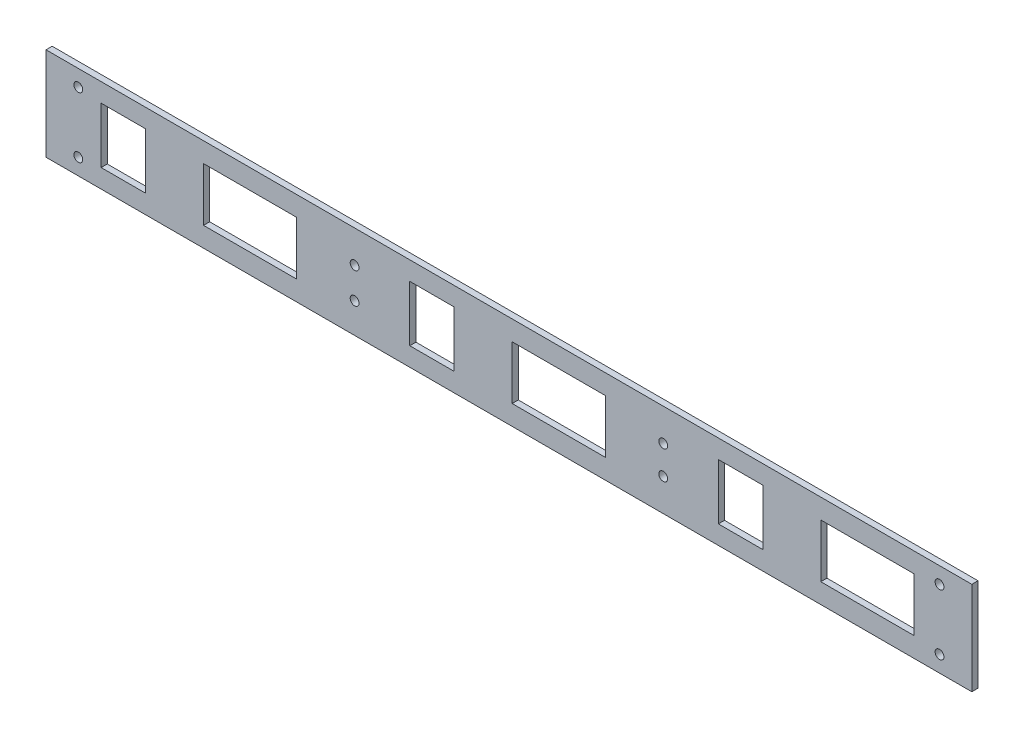
SolidWorks part; units mm, degrees
ref_plane "前基準面" through (0, 0, 0) normal (0, 0, 1) x (1, 0, 0)
ref_plane "上基準面" through (0, 0, 0) normal (0, 1, 0) x (1, 0, 0)
ref_plane "右基準面" through (0, 0, 0) normal (1, 0, 0) x (0, 0, -1)
sketch "草圖1" plane through (0, 0, 0) normal (0, 0, 1) x (1, 0, 0)
  line L2 (-75, 22.625) -> (-75, -22.625)
  line L5 (-75, 22.625) -> (75, -22.625) construction
  line L6 (-75, -22.625) -> (143.7013, 43.3499) construction
  line L7 (-48.2, 13.55) -> (-26.6, 13.55)
  line L8 (-48.2, 13.55) -> (-48.2, -13.55)
  line L9 (-48.2, -13.55) -> (-26.6, -13.55)
  line L10 (-26.6, 13.55) -> (-26.6, -13.55)
  line L11 (-48.2, 13.55) -> (-26.6, -13.55) construction
  line L12 (-48.2, -13.55) -> (-26.6, 13.55) construction
  line L17 (1.575, 13) -> (46.825, -13) construction
  line L18 (1.575, -13) -> (46.825, 13) construction
  line L30 (143.7013, 43.3499) -> (286.8623, -61.8998) construction
  line L31 (75, -22.625) -> (210.6565, 92.1351) construction
  line L32 (151.575, 13) -> (151.575, -13)
  line L33 (1.575, 13) -> (46.825, 13)
  line L34 (1.575, 13) -> (1.575, -13)
  line L35 (1.575, -13) -> (46.825, -13)
  line L39 (375, 22.625) -> (375, -22.625)
  line L48 (210.6565, 92.1351) -> (375, -22.625) construction
  line L49 (286.8623, -61.8998) -> (375, 22.625) construction
  line L50 (46.825, 13) -> (46.825, -13)
  line L51 (151.575, 13) -> (196.825, 13)
  line L52 (196.825, 13) -> (196.825, -13)
  line L53 (151.575, -13) -> (196.825, -13)
  line L54 (101.8, 13.55) -> (101.8, -13.55)
  line L55 (101.8, 13.55) -> (123.4, 13.55)
  line L64 (123.4, 13.55) -> (123.4, -13.55)
  line L65 (101.8, -13.55) -> (123.4, -13.55)
  line L66 (301.575, 13) -> (301.575, -13)
  line L67 (301.575, 13) -> (346.825, 13)
  line L68 (346.825, 13) -> (346.825, -13)
  line L69 (301.575, -13) -> (346.825, -13)
  line L70 (251.8, 13.55) -> (251.8, -13.55)
  line L71 (251.8, 13.55) -> (273.4, 13.55)
  line L72 (273.4, 13.55) -> (273.4, -13.55)
  line L73 (251.8, -13.55) -> (273.4, -13.55)
  line L74 (-75, 22.625) -> (375, -22.625) construction
  line L75 (-75, -22.625) -> (375, 22.625) construction
  line L76 (-75, 22.625) -> (375, 22.625)
  line L77 (-75, -22.625) -> (375, -22.625)
  point P0 (0, 0)
  point P6 (-37.4, 0)
  point P11 (24.2, 0)
  point P16 (-75, 0)
  point P29 (150, 0)
  point P56 (300, 0)
  dimension "D9" = 45.25
  dimension "D1" = 150
  dimension "D2" = 95.25
  dimension "D3" = 27.1
  dimension "D4" = 21.6
  dimension "D5" = 45.25
  dimension "D6" = 26
  dimension "D7" = 26.8
  dimension "D8" = 3
extrude "填料-伸長1" add sketch "草圖1" along normal blind 3 contours L2 L77 L39 L76
extrude "除料-伸長2" cut sketch "草圖1<3>" along normal blind 3 contours L10 L7 L8 L9 | L34 L33 L50 L35 | L54 L65 L64 L55 | L32 L53 L52 L51 | L70 L73 L72 L71 | L66 L69 L68 L67 region at (-37.4, 0, 0)
sketch "草圖1<3>" plane through (0, 0, 0) normal (0, 0, 1) x (1, 0, 0) same geometry as "草圖1"
sketch "草圖2" plane through (0, 0, 0) normal (0, 0, -1) x (-1, 0, 0)
  circle A0 centre (-359.3, 14.725) radius 2.15
  circle A1 centre (-359.3, -14.725) radius 2.15
  circle A2 centre (59.3, 14.725) radius 2.15
  circle A3 centre (59.3, -14.725) radius 2.15
extrude "除料-伸長3" cut sketch "草圖2" against normal blind 5
sketch "草圖3" plane through (0, 0, 0) normal (0, 0, -1) x (-1, 0, 0)
  circle A0 centre (-225.0141, 6.925) radius 2.15
  circle A1 centre (-225, -6.925) radius 2.15
  circle A2 centre (-75, 6.925) radius 2.15
  circle A3 centre (-75, -8.025) radius 2.15
extrude "除料-伸長4" cut sketch "草圖3" against normal blind 5
